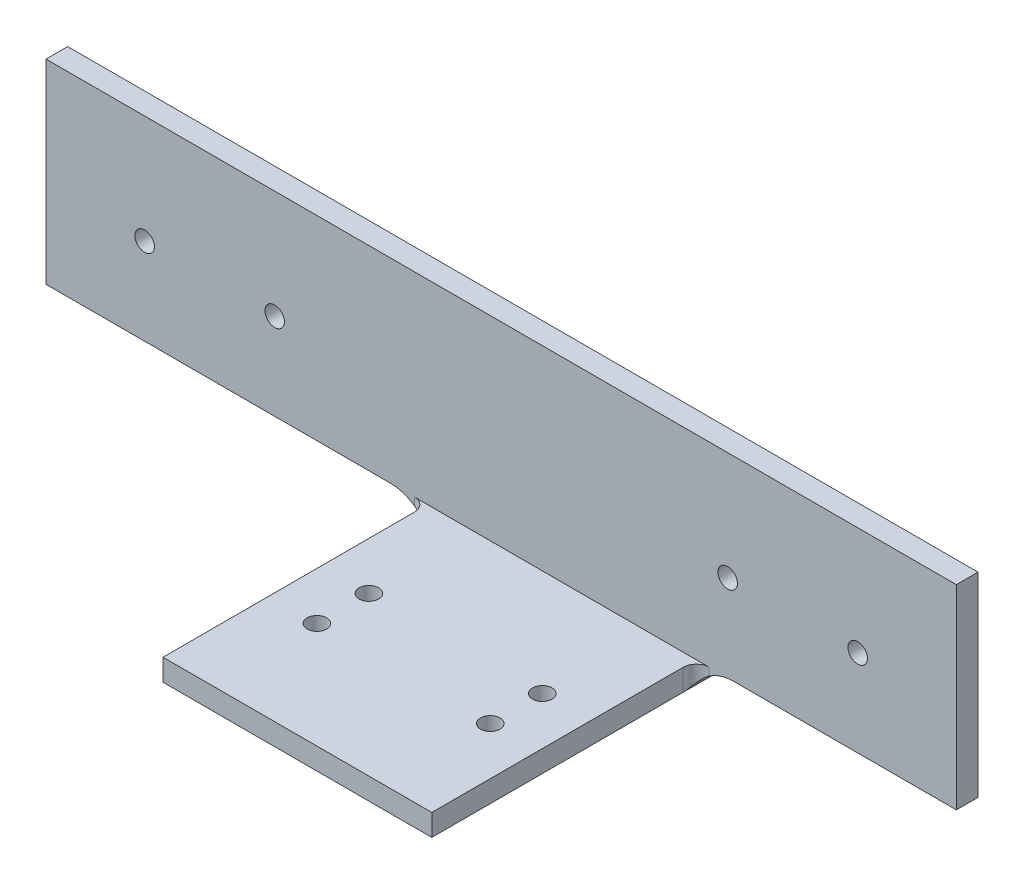
SolidWorks part; units mm, degrees
ref_plane "前视基准面" through (0, 0, 0) normal (0, 0, 1) x (1, 0, 0)
ref_plane "上视基准面" through (0, 0, 0) normal (0, 1, 0) x (1, 0, 0)
ref_plane "右视基准面" through (0, 0, 0) normal (1, 0, 0) x (0, 0, -1)
other "Configuration Table"
sketch "草图1" plane through (0, 0, 0) normal (0, 0, 1) x (1, 0, 0)
  line L1 (0, 0) -> (210, 0)
  line L2 (0, 0) -> (0, 50)
  line L3 (0, 50) -> (210, 50)
  line L4 (210, 0) -> (210, 50)
  line L5 (0, 0) -> (210, 50) construction
  line L6 (0, 50) -> (210, 0) construction
  point P4 (105, 25)
  dimension "D1" = 210
  dimension "D2" = 50
extrude "凸台-拉伸1" add sketch "草图1" along normal blind 5
sketch "草图2" plane through (0, 0, 5) normal (0, 0, 1) x (1, 0, 0)
  line L0 (150, 50) -> (150, 0) construction
  line L1 (210, 50) -> (0, 50) construction
  line L2 (0, 0) -> (210, 0) construction
  line L7 (0, 50) -> (0, 0)
  line L8 (0, 0) -> (210, 0)
  line L9 (210, 0) -> (210, 50)
  line L10 (210, 50) -> (0, 50)
  line L11 (0, 50) -> (0, 0) construction
  line L12 (0, 0) -> (210, 0) construction
  line L13 (210, 0) -> (210, 50) construction
  line L14 (210, 50) -> (0, 50) construction
  dimension "D2" = 60
  dimension "D1" = 0
sketch "草图3" plane through (0, 0, 5) normal (0, 0, 1) x (1, 0, 0)
  line L0 (172.25, 50) -> (172.25, 0) construction
  line L1 (12, 50) -> (198, 50) construction
  line L2 (12, 50) -> (12, 0) construction
  line L3 (12, 0) -> (198, 0) construction
  line L4 (0, 50) -> (0, 0)
  line L5 (0, 0) -> (210, 0)
  line L6 (210, 0) -> (210, 50)
  line L7 (210, 50) -> (0, 50)
  line L8 (0, 50) -> (0, 0) construction
  line L9 (0, 0) -> (210, 0) construction
  line L10 (210, 0) -> (210, 50) construction
  line L11 (210, 50) -> (0, 50) construction
  line L12 (198, 50) -> (198, 0) construction
  line L13 (12, 50) -> (198, 0) construction
  line L14 (12, 0) -> (198, 50) construction
  line L15 (198, 50) -> (146.5, 50) construction
  line L16 (198, 50) -> (198, 0) construction
  line L17 (198, 0) -> (146.5, 0) construction
  line L18 (146.5, 50) -> (146.5, 0) construction
  line L19 (198, 50) -> (146.5, 0) construction
  line L20 (198, 0) -> (146.5, 50) construction
  line L21 (198, 50) -> (194, 50)
  line L22 (198, 50) -> (198, 0) construction
  line L23 (198, 0) -> (194, 0)
  line L24 (194, 50) -> (194, 0) construction
  line L25 (198, 50) -> (194, 0) construction
  line L26 (198, 0) -> (194, 50) construction
  line L27 (157.25, 25) -> (187.25, 25) construction
  line L28 (105, 50) -> (105, 0) construction
  line L29 (52.75, 25) -> (22.75, 25) construction
  circle A0 centre (157.25, 25) radius 2.25
  circle A1 centre (187.25, 25) radius 2.25
  circle A2 centre (22.75, 25) radius 2.25
  circle A3 centre (52.75, 25) radius 2.25
  point P8 (105, 25)
  point P11 (172.25, 25)
  point P14 (196, 25)
  point P21 (172.25, 25)
  point P28 (14, 25)
  point P29 (37.75, 25)
  dimension "D7" = 4.5
  dimension "D8" = 4.5
  dimension "D2" = 105
  dimension "D3" = 186
  dimension "D4" = 51.5
  dimension "D5" = 4
  dimension "D6" = 30
  dimension "D9" = 25
  dimension "D1" = 0
extrude "切除-拉伸1" cut sketch "草图3" against normal blind 5 contours A2 | A3 | A0 | A1
sketch "草图4" plane through (0, 0, 5) normal (0, 0, 1) x (1, 0, 0)
  line L0 (0, 50) -> (0, 0) construction
  line L1 (210, 0) -> (0, 0)
  line L2 (210, 0) -> (210, 5)
  line L3 (210, 5) -> (0, 5)
  line L4 (0, 0) -> (0, 5)
  line L5 (210, 0) -> (0, 5) construction
  line L6 (210, 5) -> (0, 0) construction
  point P4 (105, 2.5)
  dimension "D1" = 5
extrude "凸台-拉伸2" add sketch "草图4" along normal blind 61
sketch "草图6" plane through (0, 0, 66) normal (0, 0, 1) x (1, 0, 0)
  line L0 (0, 0) -> (210, 0) construction
  line L1 (210, 5) -> (150, 5)
  line L2 (210, 5) -> (210, 0)
  line L3 (210, 0) -> (150, 0)
  line L4 (150, 5) -> (150, 0)
  line L5 (210, 5) -> (150, 0) construction
  line L6 (210, 0) -> (150, 5) construction
  point P4 (180, 2.5)
  dimension "D1" = 60
extrude "切除-拉伸2" cut sketch "草图6" against normal up to next
fillet "圆角1" radius 10 1 edges at (150, 5, 2.5)
sketch "草图7" plane through (0, 0, 66) normal (0, 0, 1) x (1, 0, 0)
  line L0 (0, 0) -> (210, 0) construction
  line L1 (150, 5) -> (91, 5) construction
  line L2 (150, 5) -> (150, 0)
  line L3 (150, 0) -> (91, 0) construction
  line L4 (91, 5) -> (91, 0) construction
  line L5 (150, 5) -> (91, 0) construction
  line L6 (150, 0) -> (91, 5) construction
  line L8 (0, 5) -> (88, 5)
  line L9 (0, 5) -> (0, 0)
  line L10 (0, 0) -> (88, 0)
  line L11 (88, 5) -> (88, 0)
  line L12 (0, 5) -> (88, 0) construction
  line L13 (0, 0) -> (88, 5) construction
  point P4 (120.5, 2.5)
  point P13 (44, 2.5)
  line M6 (150, 5) -> (0, 5)
  line M7 (0, 5) -> (0, 0)
  line M8 (0, 0) -> (150, 0)
  dimension "D1" = 59
  dimension "D2" = 3
extrude "切除-拉伸3" cut sketch "草图7" against normal up to next contours L11 M6 M7 M8 region at (44, 2.5, 66)
fillet "圆角2" radius 10 1 edges at (88, 5, 2.5)
fillet "圆角6" radius 3 2 edges at (88, 2.5, 5) (150, 2.5, 5)
sketch "草图11" plane through (0, 5, 0) normal (0, 1, 0) x (1, 0, 0)
  line L0 (210, -5) -> (0, -5) construction
  line L1 (88, -66) -> (149.9823, -66)
  line L2 (88, -66) -> (88, -5) construction
  line L3 (88, -5) -> (149.9823, -5)
  line L4 (149.9823, -66) -> (149.9823, -5) construction
  line L5 (88, -66) -> (149.9823, -5) construction
  line L6 (88, -5) -> (149.9823, -66) construction
  line L8 (88, -5) -> (149.9823, -5)
  line L9 (88, -5) -> (88, -6)
  line L10 (88, -6) -> (149.9823, -6)
  line L11 (149.9823, -5) -> (149.9823, -6)
  line L12 (88, -5) -> (149.9823, -6) construction
  line L13 (88, -6) -> (149.9823, -5) construction
  line L14 (88, -6) -> (91, -6)
  line L15 (88, -6) -> (88, -66)
  line L16 (88, -66) -> (91, -66)
  line L17 (91, -6) -> (91, -66) construction
  line L18 (88, -6) -> (91, -66) construction
  line L19 (88, -66) -> (91, -6) construction
  line L20 (149.9823, -6) -> (146.9823, -6)
  line L21 (149.9823, -6) -> (149.9823, -66)
  line L22 (149.9823, -66) -> (146.9823, -66)
  line L23 (146.9823, -6) -> (146.9823, -66) construction
  line L24 (149.9823, -6) -> (146.9823, -66) construction
  line L25 (149.9823, -66) -> (146.9823, -6) construction
  line L26 (138.9912, -41.5) -> (98.9912, -41.5) construction
  line L27 (138.9912, -41.5) -> (138.9912, -29.5) construction
  line L28 (138.9912, -29.5) -> (98.9912, -29.5) construction
  line L29 (98.9912, -41.5) -> (98.9912, -29.5) construction
  line L30 (138.9912, -41.5) -> (98.9912, -29.5) construction
  line L31 (138.9912, -29.5) -> (98.9912, -41.5) construction
  circle A0 centre (98.9912, -41.5) radius 2.25
  circle A1 centre (98.9912, -29.5) radius 2.25
  circle A2 centre (138.9912, -29.5) radius 2.25
  circle A3 centre (138.9912, -41.5) radius 2.25
  point P4 (118.9912, -35.5)
  point P10 (118.9912, -5.5)
  point P13 (89.5, -36)
  point P16 (148.4823, -36)
  point P17 (118.9912, -35.5)
  dimension "D7" = 4.5
  dimension "D1" = 61.9823
  dimension "D2" = 1
  dimension "D3" = 3
  dimension "D4" = 3
  dimension "D5" = 40
  dimension "D6" = 12
extrude "切除-拉伸4" cut sketch "草图11" against normal through all contours A1 | A2 | A0 | A3 region at (98.9912, 5, 41.5) region at (98.9912, 5, 29.5) region at (138.9912, 5, 29.5) region at (138.9912, 5, 41.5)
